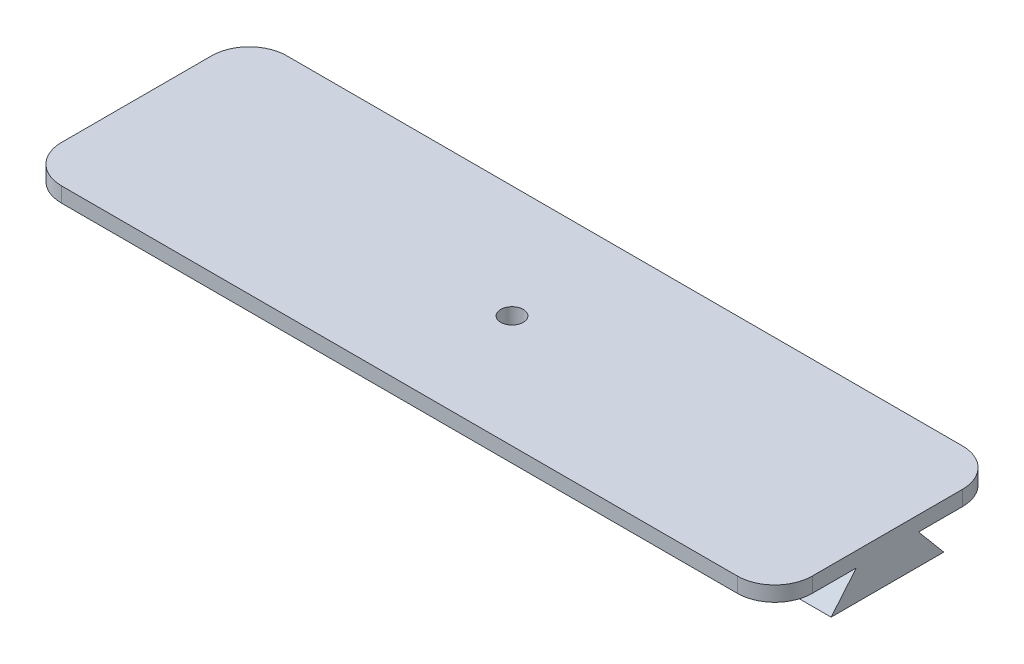
SolidWorks part; units mm, degrees
ref_plane "Front Plane" through (0, 0, 0) normal (0, 0, 1) x (1, 0, 0)
ref_plane "Top Plane" through (0, 0, 0) normal (0, 1, 0) x (1, 0, 0)
ref_plane "Right Plane" through (0, 0, 0) normal (1, 0, 0) x (0, 0, -1)
sketch "Sketch4" plane through (0, 0, 0) normal (0, 1, 0) x (1, 0, 0)
  line L1 (0, 0) -> (100, 0)
  line L2 (0, 0) -> (0, -30)
  line L3 (0, -30) -> (100, -30)
  line L4 (100, 0) -> (100, -30)
  dimension "D1" = 30
  dimension "D2" = 100
extrude "Boss-Extrude2" add sketch "Sketch4" along normal blind 6
sketch "Sketch6" plane through (100, 0, 0) normal (1, 0, 0) x (0, 0, -1)
  line L0 (-15, 6) -> (-15, 0) construction
  line L1 (-30, 6) -> (0, 6) construction
  line L2 (-30, 0) -> (0, 0) construction
  line L4 (-7.5, 0) -> (0, 0)
  line L6 (-22.5, 0) -> (-30, 0)
  line L12 (-30, 0) -> (-30, 4)
  line L13 (-30, 6) -> (-30, 0) construction
  line L14 (-30, 4) -> (-19.1436, 4)
  line L15 (-22.5, 0) -> (-19.1436, 4)
  line L16 (0, 0) -> (0, 4)
  line L17 (0, 4) -> (-10.8564, 4)
  line L18 (-7.5, 0) -> (-10.8564, 4)
  dimension "D1" = 4
  dimension "D2" = 50
  dimension "D3" = 15
  dimension "D5" = 8.2872
extrude "Cut-Extrude1" cut sketch "Sketch6" against normal through all
sketch "Sketch7" plane through (0, 6, 0) normal (0, 1, 0) x (1, 0, 0)
  line L0 (0, -15) -> (100, -15) construction
  line L1 (0, 0) -> (0, -30) construction
  line L2 (100, -30) -> (100, 0) construction
  circle A0 centre (50, -15) radius 1.5
  dimension "D1" = 3
extrude "Cut-Extrude2" cut sketch "Sketch7" against normal through all
fillet "Fillet2" radius 5 1 edges at (0, 5, 0)
fillet "Fillet3" radius 5 3 edges at (100, 5, 0) (100, 5, 30) (0, 5, 30)
